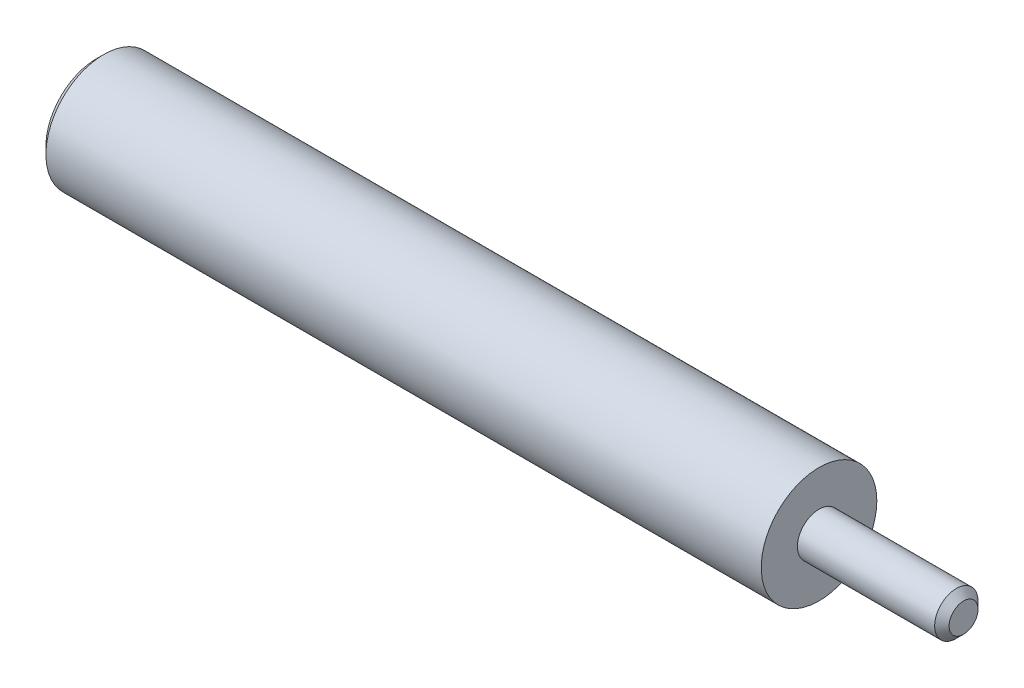
SolidWorks part; units mm, degrees
ref_plane "Alzado" through (0, 0, 0) normal (0, 0, 1) x (1, 0, 0)
ref_plane "Planta" through (0, 0, 0) normal (0, 1, 0) x (1, 0, 0)
ref_plane "Vista lateral" through (0, 0, 0) normal (1, 0, 0) x (0, 0, -1)
sketch "Croquis1" plane through (0, 0, 0) normal (1, 0, 0) x (0, 0, -1)
  circle A0 centre (0, 0) radius 4
  dimension "D1" = 8
extrude "Saliente-Extruir1" add sketch "Croquis1" along normal blind 50
sketch "Croquis2" plane through (50, 0, 0) normal (1, 0, 0) x (0, 0, -1)
  circle A0 centre (0, 0) radius 1.5
  dimension "D1" = 3
extrude "Saliente-Extruir2" add sketch "Croquis2" along normal blind 10
cosmetic thread "Rosca cosmética1" parameters "D2"=2
chamfer "Chaflán1" distance 0.5 angle 45 1 edges at (0, 0, -4)
chamfer "Chaflán2" distance 0.5 angle 45 1 edges at (60, 0, -1.5)
